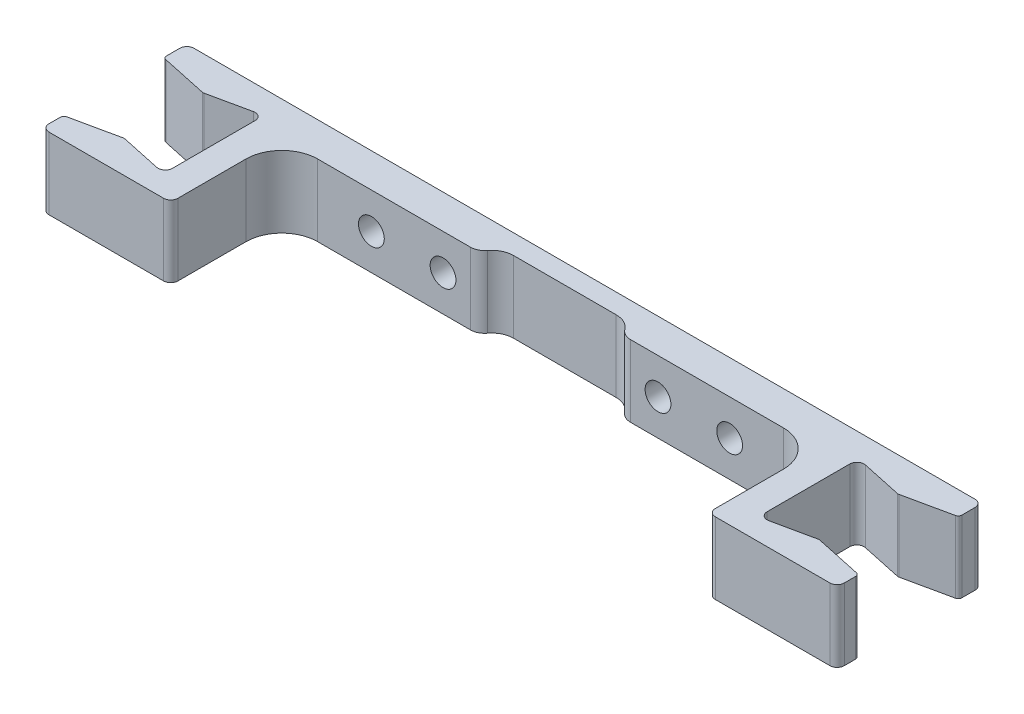
SolidWorks part; units mm, degrees
ref_plane "正面" through (0, 0, 0) normal (0, 0, 1) x (1, 0, 0)
ref_plane "平面" through (0, 0, 0) normal (0, 1, 0) x (1, 0, 0)
ref_plane "右側面" through (0, 0, 0) normal (1, 0, 0) x (0, 0, -1)
sketch "ｽｹｯﾁ1" plane through (0, 0, 0) normal (0, 0, 1) x (1, 0, 0)
  line L0 (56.5, 563.3554) -> (56.5, -236.6446) construction
  line L1 (55.5, -116) -> (-55.5, -116)
  line L2 (55.5, -116) -> (55.5, -106)
  line L3 (55.5, -106) -> (-55.5, -106)
  line L4 (-55.5, -116) -> (-55.5, -106)
  line L5 (-56.5, 563.3554) -> (-56.5, -236.6446) construction
  line L6 (0, -116) -> (0, -106) construction
  circle A0 centre (15, -111) radius 1.6 construction
  circle A1 centre (15, -111) radius 1.6 construction
  circle A2 centre (25, -111) radius 1.8
  circle A3 centre (15, -111) radius 1.8
  circle A4 centre (-15, -111) radius 1.8
  circle A5 centre (-25, -111) radius 1.8
  dimension "D3" = 5
  dimension "D4" = 5
  dimension "D5" = 3.6
  dimension "D1" = 1
  dimension "D2" = 1
extrude "ﾎﾞｽ - 押し出し1" add sketch "ｽｹｯﾁ1" along normal blind 4.75
sketch "ｽｹｯﾁ2" plane through (0, 0, 4.75) normal (0, 0, 1) x (1, 0, 0)
  line L0 (-55.5, -116) -> (55.5, -116) construction
  line L1 (41.5, -116) -> (37.5, -116)
  line L2 (41.5, -116) -> (41.5, -106)
  line L3 (41.5, -106) -> (37.5, -106)
  line L4 (37.5, -116) -> (37.5, -106)
  line L5 (55.5, -106) -> (-55.5, -106) construction
  line L6 (0, -116) -> (0, -106) construction
  line L11 (-41.5, -106) -> (-37.5, -106)
  line L12 (-37.5, -116) -> (-37.5, -106)
  line L13 (-41.5, -116) -> (-37.5, -116)
  line L14 (-41.5, -116) -> (-41.5, -106)
  line L15 (55.5, -116) -> (55.5, -106) construction
  dimension "D1" = 14
  dimension "D2" = 4
extrude "ﾎﾞｽ - 押し出し2" add sketch "ｽｹｯﾁ2" along normal blind 15.5
sketch "ｽｹｯﾁ3" plane through (41.5, 0, 0) normal (1, 0, 0) x (0, 0, -1)
  line L0 (-20.25, -106) -> (-4.75, -106) construction
  line L1 (-20.25, -116) -> (-15.75, -116)
  line L2 (-20.25, -116) -> (-20.25, -106)
  line L3 (-20.25, -106) -> (-15.75, -106)
  line L4 (-15.75, -116) -> (-15.75, -106)
  dimension "D1" = 4.5
extrude "ﾎﾞｽ - 押し出し3" add sketch "ｽｹｯﾁ3" along normal blind 14
sketch "ｽｹｯﾁ4" plane through (-41.5, 0, 0) normal (-1, 0, 0) x (0, 0, 1)
  line L0 (20.25, -106) -> (4.75, -106) construction
  line L1 (20.25, -116) -> (15.75, -116)
  line L2 (20.25, -116) -> (20.25, -106)
  line L3 (20.25, -106) -> (15.75, -106)
  line L4 (15.75, -116) -> (15.75, -106)
  dimension "D1" = 4.5
extrude "ﾎﾞｽ - 押し出し4" add sketch "ｽｹｯﾁ4" along normal blind 14
fillet "ﾌｨﾚｯﾄ1" radius 5 2 edges at (37.5, -111, 4.75) (-37.5, -111, 4.75)
fillet "ﾌｨﾚｯﾄ2" radius 1 6 edges at (55.5, -111, 0) (-55.5, -111, 0) (-55.5, -111, 20.25) (55.5, -111, 20.25) (37.5, -111, 20.25) (-37.5, -111, 20.25)
sketch "ｽｹｯﾁ5" plane through (0, -106, 0) normal (0, 1, 0) x (1, 0, 0)
  line L0 (32.5, -4.75) -> (-32.5, -4.75) construction
  line L1 (-10, -4.75) -> (10, -4.75)
  line L2 (-10, -4.75) -> (-10, -2.75)
  line L3 (-10, -2.75) -> (10, -2.75)
  line L4 (10, -4.75) -> (10, -2.75)
  line L5 (54.5, 0) -> (-54.5, 0) construction
  point P6 (0, -2.75)
  point P9 (0, 0)
  dimension "D1" = 0
  dimension "D2" = 20
  dimension "D3" = 2
extrude "ｶｯﾄ - 押し出し1" cut sketch "ｽｹｯﾁ5" against normal blind 14
fillet "ﾌｨﾚｯﾄ4" radius 3 2 edges at (10, -111, 2.75) (-10, -111, 2.75)
fillet "ﾌｨﾚｯﾄ5" radius 2 2 edges at (10, -111, 4.75) (-10, -111, 4.75)
sketch "ｽｹｯﾁ6" plane through (0, -106, 0) normal (0, 1, 0) x (1, 0, 0)
  line L0 (-48.5, -15.75) -> (-55.5, -17.25)
  line L1 (-55.5, -15.75) -> (-41.5, -15.75) construction
  line L2 (-55.5, -19.25) -> (-55.5, -15.75) construction
  line L3 (-55.5, -17.25) -> (-55.5, -15.75)
  line L4 (-55.5, -15.75) -> (-41.5, -15.75)
  line L5 (-48.5, -4.75) -> (-48.5, -15.75) construction
  line L6 (-41.5, -4.75) -> (-55.5, -4.75) construction
  line L7 (-41.5, -10.25) -> (-48.5, -10.25) construction
  line L8 (-41.5, -15.75) -> (-41.5, -4.75) construction
  line L9 (0, -2.75) -> (0, -23.4017) construction
  line L10 (7.1716, -2.75) -> (-7.1716, -2.75) construction
  line L11 (-41.5, -17.25) -> (-41.5, -15.75)
  line L12 (-48.5, -15.75) -> (-41.5, -17.25)
  line L13 (-41.5, -3.25) -> (-41.5, -4.75)
  line L14 (-48.5, -4.75) -> (-41.5, -3.25)
  line L15 (-55.5, -3.25) -> (-55.5, -4.75)
  line L16 (-48.5, -4.75) -> (-55.5, -3.25)
  line L17 (-55.5, -4.75) -> (-41.5, -4.75)
  line L18 (55.5, -3.25) -> (55.5, -4.75)
  line L19 (48.5, -4.75) -> (55.5, -3.25)
  line L20 (41.5, -3.25) -> (41.5, -4.75)
  line L21 (55.5, -4.75) -> (41.5, -4.75)
  line L22 (48.5, -4.75) -> (41.5, -3.25)
  line L23 (41.5, -17.25) -> (41.5, -15.75)
  line L24 (48.5, -15.75) -> (41.5, -17.25)
  line L25 (55.5, -17.25) -> (55.5, -15.75)
  line L26 (48.5, -15.75) -> (55.5, -17.25)
  line L27 (55.5, -15.75) -> (41.5, -15.75)
  line M22 (55.5, -19.25) -> (55.5, -15.75)
  line M23 (55.5, -15.75) -> (41.5, -15.75)
  line M25 (41.5, -4.75) -> (55.5, -4.75)
  line M26 (55.5, -4.75) -> (55.5, -1)
  line M30 (-55.5, -1) -> (-55.5, -4.75)
  line M31 (-55.5, -4.75) -> (-41.5, -4.75)
  line M33 (-41.5, -15.75) -> (-55.5, -15.75)
  line M34 (-55.5, -15.75) -> (-55.5, -19.25)
  dimension "D1" = 1.5
extrude "ｶｯﾄ - 押し出し2" cut sketch "ｽｹｯﾁ6" against normal blind 200 contours L16 M31 M30 | L14 L13 M31 | L12 L11 M33 | L0 M33 M34 | L19 M25 M26 | L22 L20 M25 | L26 M23 M22 | L24 L23 M23 region at (-53.1667, -106, 16.25) region at (-43.8333, -106, 16.25) region at (-53.1667, -106, 4.25) region at (-43.8333, -106, 4.25) region at (43.8333, -106, 4.25) region at (53.1667, -106, 4.25) region at (53.1667, -106, 16.25) region at (43.8333, -106, 16.25)
fillet "ﾌｨﾚｯﾄ6" radius 0.5 8 edges at (55.5, -111, 17.25) (48.5, -111, 15.75) (55.5, -111, 3.25) (48.5, -111, 4.75) (-55.5, -111, 17.25) (-48.5, -111, 15.75) (-55.5, -111, 3.25) (-48.5, -111, 4.75)
fillet "ﾌｨﾚｯﾄ7" radius 1 4 edges at (-41.5, -111, 17.25) (-41.5, -111, 3.25) (41.5, -111, 17.25) (41.5, -111, 3.25)
